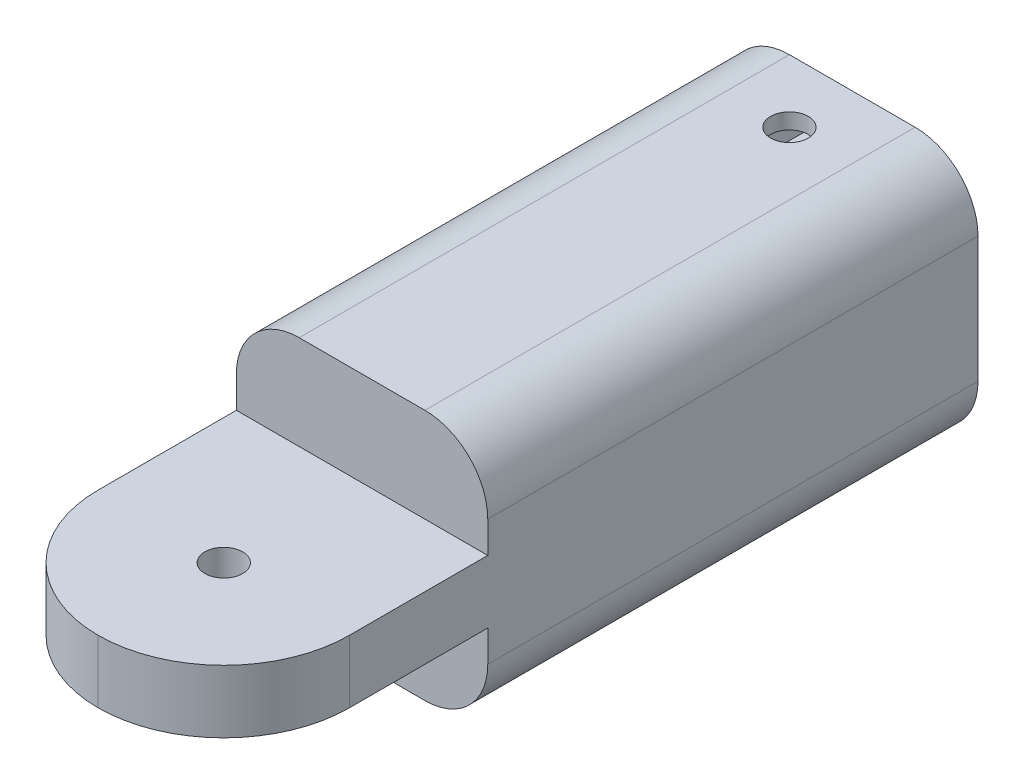
SolidWorks part; units mm, degrees
material "ABS"
ref_plane "Front Plane" through (0, 0, 0) normal (0, 0, 1) x (1, 0, 0)
ref_plane "Top Plane" through (0, 0, 0) normal (0, 1, 0) x (1, 0, 0)
ref_plane "Right Plane" through (0, 0, 0) normal (1, 0, 0) x (0, 0, -1)
sketch "Sketch1" plane through (0, 0, 0) normal (0, 0, 1) x (1, 0, 0)
  line L0 (10, 20) -> (10, 0) construction
  line L1 (0, 0) -> (20, 0)
  line L2 (0, 0) -> (0, 20)
  line L3 (0, 20) -> (20, 20)
  line L4 (20, 0) -> (20, 20)
  line L5 (0, 10) -> (20, 10) construction
  circle A0 centre (10, 10) radius 5.3
  dimension "D2" = 10.6
  dimension "D1" = 20
extrude "Boss-Extrude1" add sketch "Sketch1" along normal blind 35
sketch "Sketch2" plane through (0, 0, 35) normal (0, 0, 1) x (1, 0, 0)
  line L4 (0, 20) -> (0, 0)
  line L5 (0, 0) -> (20, 0)
  line L6 (20, 0) -> (20, 20)
  line L7 (20, 20) -> (0, 20)
  line L8 (0, 20) -> (0, 0)
  line L9 (0, 0) -> (20, 0)
  line L10 (20, 0) -> (20, 20)
  line L11 (20, 20) -> (0, 20)
  dimension "D1" = 0
extrude "Boss-Extrude2" add sketch "Sketch2" along normal blind 25
sketch "Sketch4" plane through (0, 0, 60) normal (0, 0, 1) x (1, 0, 0)
  line L0 (10, 20) -> (10, 0) construction
  line L1 (20, 20) -> (0, 20) construction
  line L2 (0, 0) -> (20, 0) construction
  line L3 (0, 10) -> (20, 10) construction
  line L4 (0, 20) -> (0, 0) construction
  line L5 (20, 0) -> (20, 20) construction
  line L10 (0, 7.5) -> (20, 7.5)
  line L11 (0, 20) -> (20, 20)
  line L12 (0, 20) -> (0, 12.5)
  line L13 (0, 12.5) -> (20, 12.5)
  line L14 (20, 20) -> (20, 12.5)
  line L15 (20, 0) -> (20, 7.5)
  line L16 (0, 0) -> (20, 0)
  line L17 (0, 0) -> (0, 7.5)
  dimension "D1" = 7.5
sketch "Sketch5" plane through (0, 20, 0) normal (0, 1, 0) x (1, 0, 0)
  line L0 (10, 0) -> (10, -60) construction
  line L1 (20, 0) -> (0, 0) construction
  line L2 (20, -60) -> (0, -60) construction
  circle A0 centre (10, -5) radius 1.5
  circle A1 centre (10, -50) radius 1.5
  dimension "D1" = 3
  dimension "D2" = 45
  dimension "D3" = 10
extrude "Cut-Extrude2" cut sketch "Sketch5" against normal up to surface (20 mm away) up to face at (10, 0, 30)
fillet "Fillet2" radius 10 2 edges at (0, 10, 60) (20, 10, 60)
extrude "Cut-Extrude3" cut sketch "Sketch4" against normal blind 21 contours L12 L11 L14 L13 | L10 L15 L16 L17
fillet "Fillet3" radius 5 4 edges at (20, 0, 19.5) (0, 0, 19.5) (0, 20, 19.5) (20, 20, 19.5)
sketch "Sketch6" plane through (0, 0, 0) normal (0, 0, -1) x (-1, 0, 0)
  line L0 (-10, 20) -> (-10, 0) construction
  line L1 (-15, 20) -> (-5, 20) construction
  line L2 (-5, 0) -> (-15, 0) construction
  line L3 (-20, 10) -> (0, 10) construction
  line L4 (-20, 5) -> (-20, 15) construction
  line L5 (0, 15) -> (0, 5) construction
  line L6 (-12.825, 17.5) -> (-7.175, 17.5) construction
  line L7 (-12.825, 18.75) -> (-7.175, 18.75)
  line L8 (-12.825, 18.75) -> (-12.825, 16.25)
  line L9 (-12.825, 16.25) -> (-7.175, 16.25)
  line L10 (-7.175, 18.75) -> (-7.175, 16.25)
  line L11 (-10, 18.75) -> (-10, 16.25) construction
  line L12 (-12.825, 2.5) -> (-7.175, 2.5) construction
  line L13 (-12.825, 3.75) -> (-7.175, 3.75)
  line L14 (-7.175, 1.25) -> (-7.175, 3.75)
  line L15 (-12.825, 1.25) -> (-7.175, 1.25)
  line L16 (-12.825, 1.25) -> (-12.825, 3.75)
  line L17 (-10, 1.25) -> (-10, 3.75) construction
  dimension "D1" = 5.65
  dimension "D2" = 2.5
  dimension "D3" = 7.5
extrude "Cut-Extrude4" cut sketch "Sketch6" against normal blind 8
chamfer "Chamfer1" distance 1 angle 45 4 edges at (12.825, 2.5, 8) (7.175, 2.5, 8) (7.175, 17.5, 8) (12.825, 17.5, 8)
